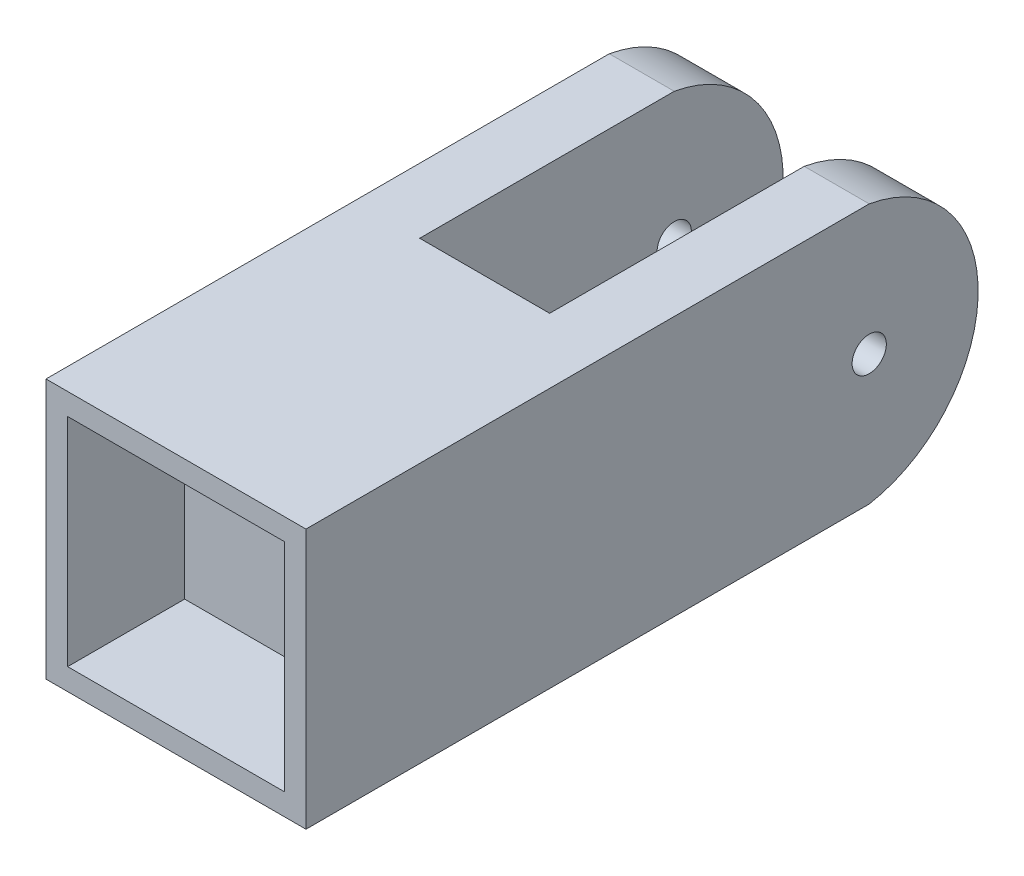
SolidWorks part; units mm, degrees
ref_plane "Front Plane" through (0, 0, 0) normal (0, 0, 1) x (1, 0, 0)
ref_plane "Top Plane" through (0, 0, 0) normal (0, 1, 0) x (1, 0, 0)
ref_plane "Right Plane" through (0, 0, 0) normal (1, 0, 0) x (0, 0, -1)
sketch "Sketch2" plane through (0, 0, 0) normal (0, 0, 1) x (1, 0, 0)
  line L1 (-30, 30) -> (30, 30)
  line L2 (-30, 30) -> (-30, -30)
  line L3 (-30, -30) -> (30, -30)
  line L4 (30, 30) -> (30, -30)
  line L5 (-30, 30) -> (30, -30) construction
  line L6 (-30, -30) -> (30, 30) construction
  point P0 (0, 0)
  dimension "D1" = 60
  dimension "D2" = 60
extrude "Boss-Extrude1" add sketch "Sketch2" along normal blind 100
ref_plane "Plane1" through (0, 0, 0) normal (0, 0, -1) x (-1, 0, 0)
sketch "Sketch3" plane through (0, 0, 0) normal (0, 0, -1) x (-1, 0, 0)
  line L0 (-30, 30) -> (30, 30) construction
  line L1 (30, -30) -> (15, -30)
  line L2 (30, -30) -> (30, 30)
  line L3 (30, 30) -> (15, 30)
  line L4 (15, -30) -> (15, 30)
  line L6 (-30, -30) -> (-15, -30)
  line L7 (-30, -30) -> (-30, 30)
  line L8 (-30, 30) -> (-15, 30)
  line L9 (-15, -30) -> (-15, 30)
  dimension "D1" = 15
  dimension "D2" = 15
extrude "Boss-Extrude2" add sketch "Sketch3" along normal blind 30
ref_plane "Plane2" through (-30, 0, 0) normal (-1, 0, 0) x (0, 0, 1)
sketch "Sketch4" plane through (-30, 0, 0) normal (-1, 0, 0) x (0, 0, 1)
  line L0 (-30, -30) -> (-30, 30)
  arc A0 (-30, -30) -> (-30, 30) centre (-24.6689, 0) cw
  dimension "D1" = 30.47
extrude "Boss-Extrude3" add sketch "Sketch4" against normal blind 15
ref_plane "Plane3" through (30, 0, 0) normal (1, 0, 0) x (0, 0, -1)
sketch "Sketch5" plane through (30, 0, 0) normal (1, 0, 0) x (0, 0, -1)
  line L0 (30, 30) -> (30, -30)
  arc A0 (30, 30) -> (30, -30) centre (24.6689, 0) cw
  dimension "D1" = 30.47
extrude "Boss-Extrude4" add sketch "Sketch5" against normal blind 15
ref_plane "Plane4" through (0, 0, 100) normal (0, 0, 1) x (1, 0, 0)
sketch "Sketch6" plane through (0, 0, 100) normal (0, 0, 1) x (1, 0, 0)
  line L0 (30, 30) -> (-30, 30) construction
  line L1 (-25, 25) -> (25, 25)
  line L2 (-25, 25) -> (-25, -25)
  line L3 (-25, -25) -> (25, -25)
  line L4 (25, 25) -> (25, -25)
  line L5 (-25, 25) -> (25, -25) construction
  line L6 (-25, -25) -> (25, 25) construction
  line L7 (30, -30) -> (30, 30) construction
  point P0 (0, 0)
  dimension "D1" = 5
  dimension "D2" = 5
extrude "Cut-Extrude1" cut sketch "Sketch6" against normal blind 27
ref_plane "Plane5" through (15, 0, 0) normal (-1, 0, 0) x (0, 0, 1)
sketch "Sketch7" plane through (15, 0, 0) normal (-1, 0, 0) x (0, 0, 1)
  line L0 (0, -30) -> (0, 30) construction
  circle A0 centre (-30, 0) radius 3.95
  dimension "D2" = 7.9
  dimension "D1" = 30
extrude "Cut-Extrude2" cut sketch "Sketch7" against normal through all
ref_plane "Plane6" through (-15, 0, 0) normal (1, 0, 0) x (0, 0, -1)
sketch "Sketch9" plane through (-15, 0, 0) normal (1, 0, 0) x (0, 0, -1)
  line L0 (0, 30) -> (0, -30) construction
  circle A0 centre (30, 0) radius 3.95
  dimension "D2" = 7.9
  dimension "D1" = 30
extrude "Cut-Extrude3" cut sketch "Sketch9" against normal through all
sketch "Sketch12" plane through (-15, 0, 0) normal (1, 0, 0) x (0, 0, -1)
  line L0 (0, 0) -> (0, 30)
  line L2 (-100, 30) -> (30, 30) construction
  line L3 (-28.7538, 30) -> (0, 30)
  line L4 (0, 0) -> (-28.7538, 30)
  line L5 (0, 0) -> (0, -30)
  line L6 (0, -30) -> (-28.7538, -30)
  line L7 (-100, -30) -> (30, -30) construction
  line L8 (-28.7538, -30) -> (0, 0)
  line M5 (0, 30) -> (0, -30)
extrude "Cut-Extrude4" cut sketch "Sketch12" along normal blind 30 contours L4 L3 M5 | L8 L6 M5 region at (-15, 20, 9.5846) region at (-15, -20, 9.5846)
fillet "Fillet1" radius 5 1 edges at (0, 0, 0)
